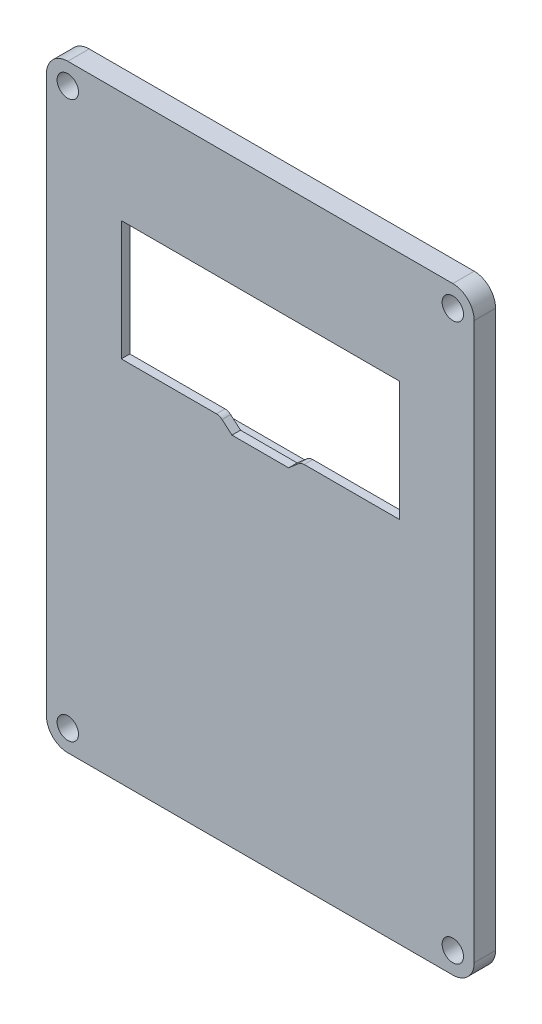
SolidWorks part; units mm, degrees
ref_plane "Front Plane" through (0, 0, 0) normal (0, 0, 1) x (1, 0, 0)
ref_plane "Top Plane" through (0, 0, 0) normal (0, 1, 0) x (1, 0, 0)
ref_plane "Right Plane" through (0, 0, 0) normal (1, 0, 0) x (0, 0, -1)
sketch "Sketch1" plane through (0, 0, 0) normal (0, 0, 1) x (1, 0, 0)
  line L0 (-40.4174, 67) -> (40.4174, 67)
  line L1 (-45, 70) -> (45, 70)
  line L2 (-50, 65) -> (-50, -65)
  line L3 (-45, -70) -> (45, -70)
  line L4 (50, 65) -> (50, -65)
  line L5 (-50, 70) -> (50, -70) construction
  line L6 (-50, -70) -> (50, 70) construction
  line L7 (-46.5164, -67) -> (-46.5, -67)
  line L8 (-47, -60.4174) -> (-47, 60.4174)
  line L11 (-42.5425, -60.6456) -> (42.5425, 60.6456) construction
  line L12 (-42.5425, 60.6456) -> (42.5425, -60.6456) construction
  line L13 (47, -60.4174) -> (47, 60.4174)
  line L14 (-40.4174, -67) -> (40.4174, -67)
  arc A0 (-50, -65) -> (-45, -70) centre (-45, -65) ccw
  arc A1 (45, -70) -> (50, -65) centre (45, -65) ccw
  arc A2 (45, 70) -> (50, 65) centre (45, 65) cw
  arc A3 (-45, 70) -> (-50, 65) centre (-45, 65) ccw
  circle A4 centre (-45, 65) radius 2.5
  circle A5 centre (45, 65) radius 2.5
  circle A6 centre (45, -65) radius 2.5
  circle A7 centre (-45, -65) radius 2.5
  arc A8 (-45, 70) -> (-50, 65) centre (-45, 65) ccw
  arc A9 (40.4174, 67) -> (47, 60.4174) centre (45, 65) ccw
  arc A10 (47, -60.4174) -> (40.4174, -67) centre (45, -65) ccw
  arc A11 (-50, -65) -> (-45, -70) centre (-45, -65) ccw
  arc A12 (50, 65) -> (45, 70) centre (45, 65) ccw
  arc A13 (45, -70) -> (50, -65) centre (45, -65) ccw
  arc A14 (-40.4174, -67) -> (-47, -60.4174) centre (-45, -65) ccw
  arc A15 (-47, 60.4174) -> (-40.4174, 67) centre (-45, 65) ccw
  point P0 (0, 0)
  point P29 (0, 0)
  dimension "D3" = 5
  dimension "D4" = 5
  dimension "D1" = 140
  dimension "outerWidth" = 100
extrude "Boss-Extrude1" add sketch "Sketch1" along normal blind 5 contours A15 L8 A14 L14 A10 L13 A9 L0 | L1 A3 L2 A0 L3 A1 L4 A2 A6 A5 A4 A7 L8 A15 L0 A9 L13 A10 L14 A14 region at (0, 0, 0) region at (0, 68.2795, 0)
sketch "Sketch2" plane through (0, 0, 0) normal (0, 0, -1) x (-1, 0, 0)
  line L0 (-8.9358, 15.5099) -> (-6.6219, 13.5)
  line L1 (-32.5, 16) -> (-10.2473, 16)
  line L2 (-32.5, 16) -> (-32.5, 44)
  line L3 (-32.5, 44) -> (32.5, 44)
  line L4 (32.5, 16) -> (32.5, 44)
  line L5 (-32.5, 16) -> (32.5, 44) construction
  line L6 (-32.5, 44) -> (32.5, 16) construction
  line L7 (-6.6219, 13.5) -> (6.6219, 13.5)
  line L8 (0, 2.75) -> (0, -2.75) construction
  line L9 (32.5, 16) -> (10.2473, 16)
  line L10 (8.9358, 15.5099) -> (6.6219, 13.5)
  line L12 (-38, 12) -> (38, 12)
  line L13 (-38, 12) -> (-38, 48)
  line L14 (-38, 48) -> (38, 48)
  line L15 (38, 12) -> (38, 48)
  line L16 (-38, 12) -> (38, 48) construction
  line L17 (-38, 48) -> (38, 12) construction
  arc A0 (-10.2473, 16) -> (-8.9358, 15.5099) centre (-10.2473, 14) cw
  arc A1 (10.2473, 16) -> (8.9358, 15.5099) centre (10.2473, 14) ccw
  point P0 (0, 30)
  point P9 (0, 30)
  point P23 (0, 13.5)
  dimension "D3" = 2
  dimension "D1" = 30
  dimension "D2" = 65
  dimension "D4" = 36
  dimension "D5" = 2.5
  dimension "D6" = 76
extrude "Cut-Extrude1" cut sketch "Sketch2" against normal blind 5 contours A1 L9 L4 L3 L2 L1 A0 L0 L12 L10 region at (0, 29.6703, 0)
extrude "Cut-Extrude2" cut sketch "Sketch2<4>" against normal blind 3
sketch "Sketch2<4>" plane through (0, 0, 0) normal (0, 0, -1) x (-1, 0, 0) same geometry as "Sketch2"
